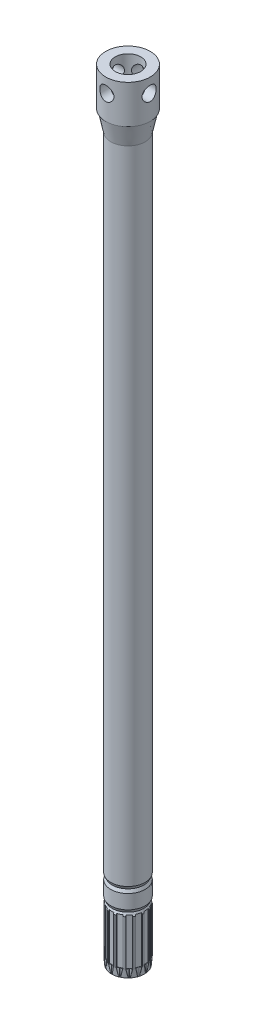
SolidWorks part; units mm, degrees
ref_plane "Front Plane" through (0, 0, 0) normal (0, 0, 1) x (1, 0, 0)
ref_plane "Top Plane" through (0, 0, 0) normal (0, 1, 0) x (1, 0, 0)
ref_plane "Right Plane" through (0, 0, 0) normal (1, 0, 0) x (0, 0, -1)
sketch "Sketch3" plane through (0, 0, 0) normal (0, 1, 0) x (1, 0, 0)
  circle A0 centre (0, 0) radius 10.795
  circle A1 centre (0, 0) radius 8.001
  dimension "D1" = 21.59
  dimension "D2" = 16.002
extrude "Boss-Extrude1" add sketch "Sketch3" along normal blind 393.7
sketch "Sketch4" plane through (0, 393.7, 0) normal (0, 1, 0) x (1, 0, 0)
  circle A0 centre (0, 0) radius 10.795
  dimension "D2" = 21.59
extrude "Boss-Extrude2" add sketch "Sketch4" along normal blind 12.7 draft 12 draft outward yes
sketch "Sketch6" plane through (0, 406.4, 0) normal (0, 1, 0) x (1, 0, 0)
  circle A0 centre (0, 0) radius 8.001
  dimension "D1" = 16.002
extrude "Cut-Extrude1" cut sketch "Sketch6" against normal blind 50.8
sketch "Sketch7" plane through (0, 406.4, 0) normal (0, 1, 0) x (1, 0, 0)
  circle A0 centre (0, 0) radius 13.97
  circle A1 centre (0, 0) radius 8.001
  dimension "D1" = 16.002
  dimension "D2" = 27.94
extrude "Boss-Extrude4" add sketch "Sketch7" along normal blind 24.13
sketch "Sketch8" plane through (0, 0, 0) normal (1, 0, 0) x (0, 0, -1)
  line L0 (-13.97, 430.53) -> (-13.97, 406.4) construction
  line L2 (13.97, 430.53) -> (-13.97, 430.53) construction
  circle A0 centre (0, 421.64) radius 4.445
  dimension "D3" = 8.89
  dimension "D1" = 13.97
  dimension "D2" = 8.89
extrude "Cut-Extrude2" cut sketch "Sketch8" against normal blind 50.8 and the other way blind 50.8
pattern_circular "CirPattern1" count 2 over 90 about axis through (0, 430.53, 0) along (0, 1, 0) of "Cut-Extrude2"
sketch "Sketch9" plane through (0, 0, 0) normal (0, -1, 0) x (-1, 0, 0)
  circle A0 centre (0, 0) radius 10.795 construction
  circle A1 centre (0, 0) radius 8.001 construction
  circle A2 centre (0, 0) radius 10.795
  circle A3 centre (0, 0) radius 8.001
extrude "Boss-Extrude5" add sketch "Sketch9" along normal blind 8.89
sketch "Sketch10" plane through (0, -8.89, 0) normal (0, -1, 0) x (-1, 0, 0)
  circle A0 centre (0, 0) radius 10.795 construction
  circle A1 centre (0, 0) radius 10.795
extrude "Boss-Extrude6" add sketch "Sketch10" along normal blind 1.905 draft 25
sketch "Sketch11" plane through (0, -10.795, 0) normal (0, -1, 0) x (1, 0, 0)
  circle A0 centre (0, 0) radius 8.001
  dimension "D1" = 16.002
extrude "Cut-Extrude3" cut sketch "Sketch11" against normal blind 50.8
sketch "Sketch12" plane through (0, -10.795, 0) normal (0, -1, 0) x (1, 0, 0)
  circle A0 centre (0, 0) radius 9.9067 construction
  circle A1 centre (0, 0) radius 9.9067
extrude "Boss-Extrude7" add sketch "Sketch12" along normal blind 1.905 draft 25 draft outward yes
sketch "Sketch13" plane through (0, -12.7, 0) normal (0, -1, 0) x (1, 0, 0)
  circle A0 centre (0, 0) radius 8.001
  dimension "D1" = 16.002
extrude "Cut-Extrude4" cut sketch "Sketch13" against normal blind 50.8
sketch "Sketch14" plane through (0, -12.7, 0) normal (0, -1, 0) x (1, 0, 0)
  circle A0 centre (0, 0) radius 10.795 construction
  circle A1 centre (0, 0) radius 8.001 construction
  circle A2 centre (0, 0) radius 10.795
  circle A3 centre (0, 0) radius 8.001
extrude "Boss-Extrude8" add sketch "Sketch14" along normal blind 8.89
sketch "Sketch15" plane through (0, -21.59, 0) normal (0, -1, 0) x (1, 0, 0)
  circle A0 centre (0, 0) radius 10.795 construction
  circle A1 centre (0, 0) radius 10.795
extrude "Boss-Extrude9" add sketch "Sketch15" along normal blind 1.905 draft 25
sketch "Sketch16" plane through (0, -23.495, 0) normal (0, -1, 0) x (1, 0, 0)
  circle A0 centre (0, 0) radius 8.001
  dimension "D1" = 16.002
extrude "Cut-Extrude5" cut sketch "Sketch16" against normal blind 50.8
sketch "Sketch19" plane through (0, -23.495, 0) normal (0, -1, 0) x (1, 0, 0)
  circle A0 centre (0, 0) radius 9.9067 construction
  circle A1 centre (0, 0) radius 9.9067
extrude "Boss-Extrude11" add sketch "Sketch19" along normal blind 1.905 draft 25 draft outward yes
sketch "Sketch20" plane through (0, -25.4, 0) normal (0, -1, 0) x (1, 0, 0)
  circle A0 centre (0, 0) radius 8.001
  dimension "D1" = 16.002
extrude "Cut-Extrude6" cut sketch "Sketch20" against normal blind 50.8
sketch "Sketch21" plane through (0, -25.4, 0) normal (0, -1, 0) x (1, 0, 0)
  circle A0 centre (0, 0) radius 8.001 construction
  circle A1 centre (0, 0) radius 10.795 construction
  circle A2 centre (0, 0) radius 8.001
  circle A3 centre (0, 0) radius 10.795
extrude "Boss-Extrude12" add sketch "Sketch21" along normal blind 28.448
sketch "Sketch22" plane through (0, -53.848, 0) normal (0, -1, 0) x (1, 0, 0)
  line L0 (0, 0) -> (0, 10.795) construction
  line L1 (0, 0) -> (-1.524, 0) construction
  line L2 (-1.524, 0) -> (-1.524, 10.6869) construction
  line L3 (0, 0) -> (1.524, 0) construction
  line L4 (1.524, 0) -> (1.524, 10.6869) construction
  line L5 (-1.524, 10.16) -> (1.524, 10.16)
  line L6 (1.524, 10.16) -> (1.524, 10.6869)
  line L7 (-1.524, 10.16) -> (-1.524, 10.6869)
  circle A0 centre (0, 0) radius 10.795 construction
  circle A1 centre (0, 0) radius 10.795 construction
  arc A2 (1.524, 10.6869) -> (-1.524, 10.6869) centre (0, 0) ccw
  dimension "D1" = 1.524
  dimension "D2" = 1.524
  dimension "D3" = 10.16
extrude "Cut-Extrude7" cut sketch "Sketch22" against normal blind 29.21 and the other way blind 5.08
pattern_circular "CirPattern2" count 15 over 360 about axis through (0, -53.848, 0) along (0, 1, 0) of "Cut-Extrude7"
sketch "Sketch23" plane through (0, -53.848, 0) normal (0, -1, 0) x (1, 0, 0)
  circle A0 centre (0, 0) radius 10.795
  circle A1 centre (0, 0) radius 8.001
  dimension "D1" = 21.59
  dimension "D2" = 16.002
extrude "Boss-Extrude13" add sketch "Sketch23" along normal blind 5.08 draft 5
fillet "Fillet1" radius 0.254 30 edges at (-8.4931, -39.624, -6.6633) (-7.5145, -39.624, -7.7501) (5.739, -39.624, 9.1431) (6.9221, -39.624, 8.2835) (8.9617, -39.624, 6.0184) (9.6929, -39.624, 4.7518) (10.6348, -39.624, 1.853) (10.7876, -39.624, 0.3986) (10.469, -39.624, -2.6327) (10.0171, -39.624, -4.0236) (8.4931, -39.624, -6.6633) (7.5145, -39.624, -7.7501) (-4.739, -39.243, -9.1154) (-3.7126, -39.624, -10.1365) (-0.7312, -39.624, -10.7702) (0.7312, -39.624, -10.7702) (3.7126, -39.624, -10.1365) (5.0486, -39.624, -9.5417) (-1.524, -39.624, 10.6869) (-2.9545, -39.624, 10.3828) (-5.739, -39.624, 9.1431) (-6.9221, -39.624, 8.2835) (-8.9617, -39.624, 6.0184) (-9.6929, -39.624, 4.7518) (-10.6348, -39.624, 1.853) (-10.2636, -39.243, 0.4536) (-10.469, -39.624, -2.6327) (-9.5608, -39.243, -3.7602) (1.524, -39.624, 10.6869) (2.7402, -39.243, 9.9015)
sketch "Sketch24" plane through (0, -58.928, 0) normal (0, -1, 0) x (1, 0, 0)
  line L0 (0, 0) -> (-1.524, 0) construction
  line L1 (-1.524, 0) -> (-1.524, 8.3068) construction
  line L2 (-1.524, 8.3068) -> (-1.524, 10.6869) construction
  line L3 (0, 0) -> (1.524, 0) construction
  line L4 (1.524, 0) -> (1.524, 10.6869) construction
  line L5 (0, 0) -> (0, 10.795) construction
  line L9 (-1.524, 10.6869) -> (0, 10.2242)
  line L10 (0, 10.2242) -> (1.524, 10.6869)
  circle A0 centre (0, 0) radius 8.4454 construction
  circle A1 centre (0, 0) radius 10.795 construction
  arc A3 (1.524, 10.6869) -> (-1.524, 10.6869) centre (0, 0) ccw
  point P8 (0, 0)
  dimension "D3" = 9.7832
  dimension "D1" = 1.524
  dimension "D2" = 1.524
extrude "Cut-Extrude10" cut sketch "Sketch24" against normal blind 5.08
pattern_circular "CirPattern5" count 15 over 360 about axis through (0, -58.928, 0) along (0, -1, 0) of "Cut-Extrude10"
fillet "Fillet2" radius 0.508 45 edges at (-4.1585, -56.388, 9.3403) (4.1585, -56.388, 9.3403) (0, -56.388, 10.2242) (7.598, -56.388, 6.8413) (9.7238, -56.388, 3.1594) (10.1682, -56.388, -1.0687) (8.8544, -56.388, -5.1121) (6.0096, -56.388, -8.2715) (2.1257, -56.388, -10.0008) (-2.1257, -56.388, -10.0008) (-6.0096, -56.388, -8.2715) (-8.8544, -56.388, -5.1121) (-10.1682, -56.388, -1.0687) (-9.7238, -56.388, 3.1594) (-7.598, -56.388, 6.8413)
equation "\"Pipe_OD\"= 0.85in"
equation "\"Pipe_Thickness\"= .15in"
equation "\"Pipe_Length\"= 15.5in"
equation "\"D2@Sketch3\"=\"Pipe_ID\""
equation "\"D1@Sketch3\"=\"Pipe_OD\""
equation "\"D1@Boss-Extrude1\"=\"Pipe_Length\""
equation "\"D2@Sketch4\"=\"Pipe_OD\""
equation "\"D1@Sketch6\"=\"Pipe_ID\""
equation "\"Couple_OD\"= 1.1in"
equation "\"D1@Sketch7\"=\"Pipe_ID\""
equation "\"D2@Sketch7\"=\"Couple_OD\""
equation "\"Pipe_ID\" = 0.63in"
equation "\"D1@Sketch11\"=\"Pipe_ID\""
equation "\"D1@Sketch13\"=\"Pipe_ID\""
equation "\"D1@Sketch16\"=\"Pipe_ID\""
equation "\"D1@Sketch20\"=\"Pipe_ID\""
equation "\"D1@Sketch23\"=\"Pipe_OD\""
equation "\"D2@Sketch23\"=\"Pipe_ID\""
